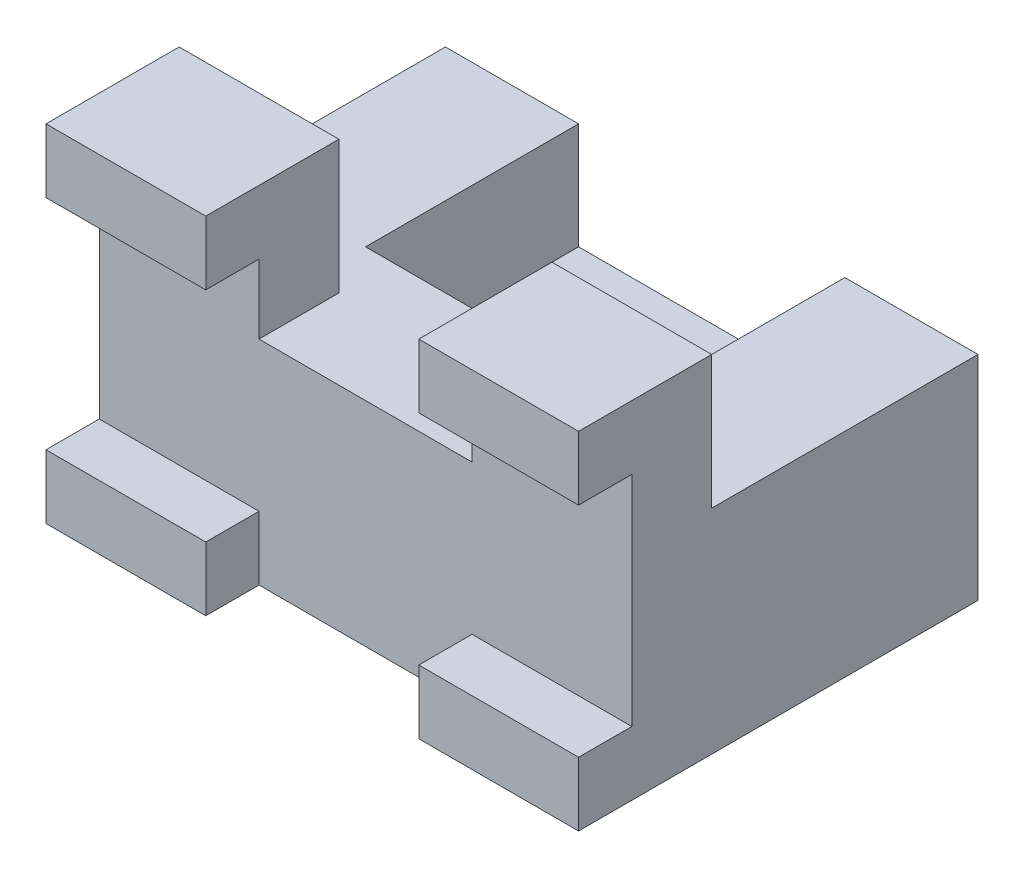
SolidWorks part; units mm, degrees
ref_plane "Front Plane" through (0, 0, 0) normal (0, 0, 1) x (1, 0, 0)
ref_plane "Top Plane" through (0, 0, 0) normal (0, 1, 0) x (1, 0, 0)
ref_plane "Right Plane" through (0, 0, 0) normal (1, 0, 0) x (0, 0, -1)
sketch "Sketch1" plane through (0, 0, 0) normal (0, 1, 0) x (1, 0, 0)
  line L0 (0, 0) -> (0, 75)
  line L1 (0, 75) -> (100, 75)
  line L2 (100, 75) -> (100, 0)
  line L3 (100, 0) -> (70, 0)
  line L4 (70, 0) -> (70, 25)
  line L5 (70, 25) -> (100, 25)
  line L6 (0, 25) -> (30, 25)
  line L7 (30, 25) -> (30, 0)
  line L8 (30, 0) -> (0, 0)
  line L9 (30, 10) -> (70, 10)
  line L10 (25, 75) -> (25, 35)
  line L11 (25, 35) -> (75, 35)
  line L12 (75, 35) -> (75, 75)
  point P15 (0, 0)
  point P18 (0, 0)
  dimension "D1" = 100
  dimension "D2" = 25
  dimension "D3" = 25
  dimension "D4" = 40
  dimension "D5" = 75
  dimension "D6" = 30
  dimension "D7" = 30
  dimension "D8" = 25
  dimension "D9" = 10
extrude "Boss-Extrude1" add sketch "Sketch1" along normal blind 40 contours L12 L11 L10 L1 L0 L6 L7 L9 L4 L5 L2 region at (1.1927, 0, -50)
extrude "Boss-Extrude2" add sketch "Sketch1<3>" along normal blind 20 contours L11 L12 L1 L10 region at (50, 0, -55)
sketch "Sketch1<3>" plane through (0, 0, 0) normal (0, 1, 0) x (1, 0, 0) same geometry as "Sketch1"
extrude "Boss-Extrude3" add sketch "Sketch1<4>" along normal blind 65 contours L5 L4 L3 L2 | L8 L7 L6 L0 region at (15, 0, -12.5) region at (85, 0, -12.5)
sketch "Sketch1<4>" plane through (0, 0, 0) normal (0, 1, 0) x (1, 0, 0) same geometry as "Sketch1"
ref_plane "Plane1" through (100, 0, 0) normal (1, 0, 0) x (0, 0, -1)
sketch "Sketch2" plane through (100, 0, 0) normal (1, 0, 0) x (0, 0, -1)
  line L0 (0, 53) -> (10, 53)
  line L1 (0, 65) -> (0, 0) construction
  line L2 (10, 53) -> (10, 12)
  line L3 (10, 12) -> (0, 12)
  line L4 (0, 53) -> (0, 65)
  line L5 (0, 65) -> (25, 65)
  line L6 (25, 65) -> (25, 40)
  line L7 (25, 40) -> (75, 40)
  line L8 (75, 40) -> (75, 0)
  line L9 (75, 0) -> (0, 0)
  line L11 (0, 12) -> (0, 0)
  line L12 (0, 12) -> (0, 0)
  line L13 (0, 53) -> (0, 12)
  dimension "D1" = 12
  dimension "D2" = 10
extrude "Cut-Extrude1" cut sketch "Sketch2" against normal through all contours L0 L13 L3 L2 region at (100, 32.5, -5)
